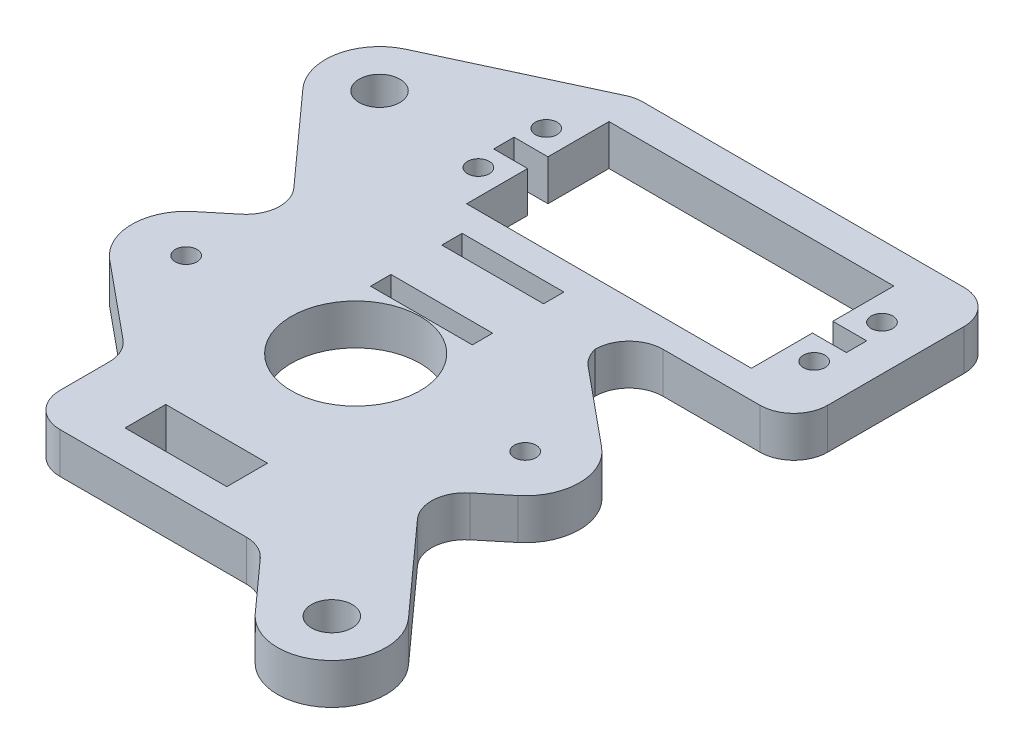
SolidWorks part; units mm, degrees
material "MDF"
ref_plane "Plano frontal" through (0, 0, 0) normal (0, 0, 1) x (1, 0, 0)
ref_plane "Plano superior" through (0, 0, 0) normal (0, 1, 0) x (1, 0, 0)
ref_plane "Plano direito" through (0, 0, 0) normal (1, 0, 0) x (0, 0, -1)
ref_plane "Plano1" through (0, -6, 0) normal (0, -1, 0) x (1, 0, 0)
sketch "Esboço1" plane through (0, -6, 0) normal (0, -1, 0) x (1, 0, 0)
  line L0 (30.7936, -136.5537) -> (52.8946, -146.8291)
  line L1 (55.0026, -147.2952) -> (102.3526, -147.2952)
  line L2 (107.3526, -142.2952) -> (107.3526, -122.2)
  line L3 (102.3526, -117.2) -> (88.05, -117.2)
  line L4 (83.05, -112.2) -> (83.05, -88.8837)
  line L5 (84.3343, -85.538) -> (103.6789, -64.0537)
  line L6 (91.7885, -53.3476) -> (85.0372, -60.8457)
  line L7 (81.3215, -62.5) -> (53.85, -62.5)
  line L8 (48.85, -67.5) -> (48.85, -99.1163)
  line L9 (47.5657, -102.462) -> (28.2211, -123.9463)
  line L10 (73.45, -114.2) -> (73.45, -117.2)
  line L11 (73.45, -117.2) -> (58.45, -117.2)
  line L12 (58.45, -117.2) -> (58.45, -114.2)
  line L13 (58.45, -114.2) -> (73.45, -114.2)
  line L14 (58.45, -108) -> (58.45, -105)
  line L15 (58.45, -105) -> (73.45, -105)
  line L16 (73.45, -105) -> (73.45, -108)
  line L17 (73.45, -108) -> (58.45, -108)
  line L18 (58.45, -67.5) -> (73.45, -67.5)
  line L19 (73.45, -67.5) -> (73.45, -73.5)
  line L20 (73.45, -73.5) -> (58.45, -73.5)
  line L21 (58.45, -73.5) -> (58.45, -67.5)
  line L22 (55.0026, -142.2952) -> (55.0026, -121.2952)
  line L23 (55.0026, -121.2952) -> (97.0026, -121.2952)
  line L24 (97.0026, -121.2952) -> (97.0026, -142.2952)
  line L25 (97.0026, -142.2952) -> (55.0026, -142.2952)
  line L26 (34.1663, -129.2994) -> (97.7337, -58.7006) construction
  line L27 (40.95, -94) -> (90.95, -94) construction
  line L28 (43.7625, -106.6859) -> (35.8615, -100.1731)
  line L29 (35.8615, -87.8269) -> (48.85, -77.1204)
  line L30 (83.05, -110.8796) -> (96.0385, -100.1731)
  line L31 (96.0385, -87.8269) -> (88.1375, -81.3141)
  arc A0 (52.8946, -146.8291) -> (55.0026, -147.2952) centre (55.0026, -142.2952) ccw
  arc A1 (102.3526, -147.2952) -> (107.3526, -142.2952) centre (102.3526, -142.2952) ccw
  arc A2 (107.3526, -122.2) -> (102.3526, -117.2) centre (102.3526, -122.2) ccw
  arc A3 (88.05, -117.2) -> (83.05, -112.2) centre (88.05, -112.2) cw
  arc A4 (83.05, -88.8837) -> (84.3343, -85.538) centre (88.05, -88.8837) cw
  arc A5 (103.6789, -64.0537) -> (91.7885, -53.3476) centre (97.7337, -58.7006) ccw
  arc A6 (85.0372, -60.8457) -> (81.3215, -62.5) centre (81.3215, -57.5) cw
  arc A7 (53.85, -62.5) -> (48.85, -67.5) centre (53.85, -67.5) ccw
  arc A8 (48.85, -99.1163) -> (47.5657, -102.462) centre (43.85, -99.1163) cw
  arc A9 (28.2211, -123.9463) -> (30.7936, -136.5537) centre (34.1663, -129.2994) ccw
  circle A10 centre (65.95, -94) radius 9.5
  circle A11 centre (40.95, -94) radius 1.6
  circle A12 centre (90.95, -94) radius 1.6
  arc A13 (35.8615, -100.1731) -> (35.8615, -87.8269) centre (40.95, -94) cw
  arc A14 (96.0385, -100.1731) -> (96.0385, -87.8269) centre (90.95, -94) ccw
  circle A15 centre (100.7526, -126.7952) radius 1.6
  circle A16 centre (100.7526, -136.7952) radius 1.6
  circle A17 centre (51.2526, -126.7952) radius 1.6
  circle A18 centre (51.2526, -136.7952) radius 1.6
  circle A19 centre (34.1663, -129.2994) radius 3
  circle A20 centre (97.7337, -58.7006) radius 3
  point P37 (65.95, -105)
  point P41 (65.95, -94)
  point P68 (32.95, -94)
  point P74 (98.95, -94)
  dimension "D16" = 3.2
  dimension "D20" = 6
  dimension "D25" = 5
  dimension "D27" = 19
  dimension "D1" = 42
  dimension "D2" = 21
  dimension "D3" = 10
  dimension "D4" = 49.5
  dimension "D5" = 95
  dimension "D6" = 3
  dimension "D7" = 15
  dimension "D8" = 34.2
  dimension "D9" = 6
  dimension "D10" = 14.6974
  dimension "D11" = 32.7952
  dimension "D12" = 40.7
  dimension "D13" = 6.2
  dimension "D14" = 5
  dimension "D15" = 5
  dimension "D17" = 5.5
  dimension "D18" = 3.75
  dimension "D19" = 48
  dimension "D21" = 8
  dimension "D22" = 9.6
  dimension "D23" = 6.6
  dimension "D24" = 4.0952
  dimension "D26" = 11
  dimension "D28" = 50
  dimension "D29" = 8
  dimension "D30" = 30
  dimension "D31" = 30
extrude "Ressalto-extrusão1" add sketch "Esboço1" against normal blind 6 contours L9 A9 L0 A0 L1 A1 L2 A2 L3 A3 L4 A4 L5 A5 L6 A6 L7 A7 L8 A8 A19 A17 A15 L12 L13 L10 L11 L16 L17 L14 L15 L20 L21 L18 L19 L24 L25 L22 L23 | L30 A14 L31 L5 A4 L4 A12 | A13 L28 L9 A8 L8 L29 A11 region at (68.7945, -6, -103.5655) region at (42.3472, -6, -92.9395) region at (89.5528, -6, -95.0605)
fillet "Filete1" radius 5 4 edges at (83.05, -3, -110.8796) (88.1375, -3, -81.3141) (48.85, -3, -77.1204) (43.7625, -3, -106.6859)
sketch "Esboço2" plane through (0, -6, 0) normal (0, -1, 0) x (1, 0, 0)
  line L1 (58.45, -105) -> (73.45, -105)
  line L2 (58.45, -105) -> (58.45, -103.7)
  line L3 (58.45, -103.7) -> (73.45, -103.7)
  line L4 (73.45, -105) -> (73.45, -103.7)
  line L9 (55.0026, -142.2952) -> (55.0026, -121.2952) construction
  line L10 (50.0026, -133.2952) -> (55.0026, -133.2952)
  line L11 (50.0026, -133.2952) -> (50.0026, -130.2952)
  line L12 (50.0026, -130.2952) -> (55.0026, -130.2952)
  line L13 (55.0026, -133.2952) -> (55.0026, -130.2952)
  line L14 (52.5026, -130.2952) -> (52.5026, -133.2952) construction
  line L15 (50.0026, -131.7952) -> (55.0026, -131.7952) construction
  line L16 (76.0026, -121.2952) -> (76.0026, -142.2952) construction
  line L17 (55.0026, -121.2952) -> (97.0026, -121.2952) construction
  line L18 (97.0026, -142.2952) -> (55.0026, -142.2952) construction
  line L19 (102.0026, -130.2952) -> (97.0026, -130.2952)
  line L20 (97.0026, -133.2952) -> (97.0026, -130.2952)
  line L21 (102.0026, -133.2952) -> (97.0026, -133.2952)
  line L22 (102.0026, -133.2952) -> (102.0026, -130.2952)
  point P5 (52.5026, -131.7952)
  point P24 (76.0026, -131.7952)
  dimension "D1" = 1.3
  dimension "D2" = 3
  dimension "D3" = 5
extrude "Corte-extrusão1" cut sketch "Esboço2" against normal through all
sketch "Esboço3" plane through (0, -6, 0) normal (0, -1, 0) x (1, 0, 0)
  line L0 (73.45, -103.7) -> (73.45, -108) construction
  line L1 (58.45, -108) -> (73.45, -108)
  line L2 (58.45, -108) -> (58.45, -106.7)
  line L3 (58.45, -106.7) -> (73.45, -106.7)
  line L4 (73.45, -108) -> (73.45, -106.7)
  dimension "D1" = 1.3
extrude "Ressalto-extrusão2" add sketch "Esboço3" against normal blind 6
